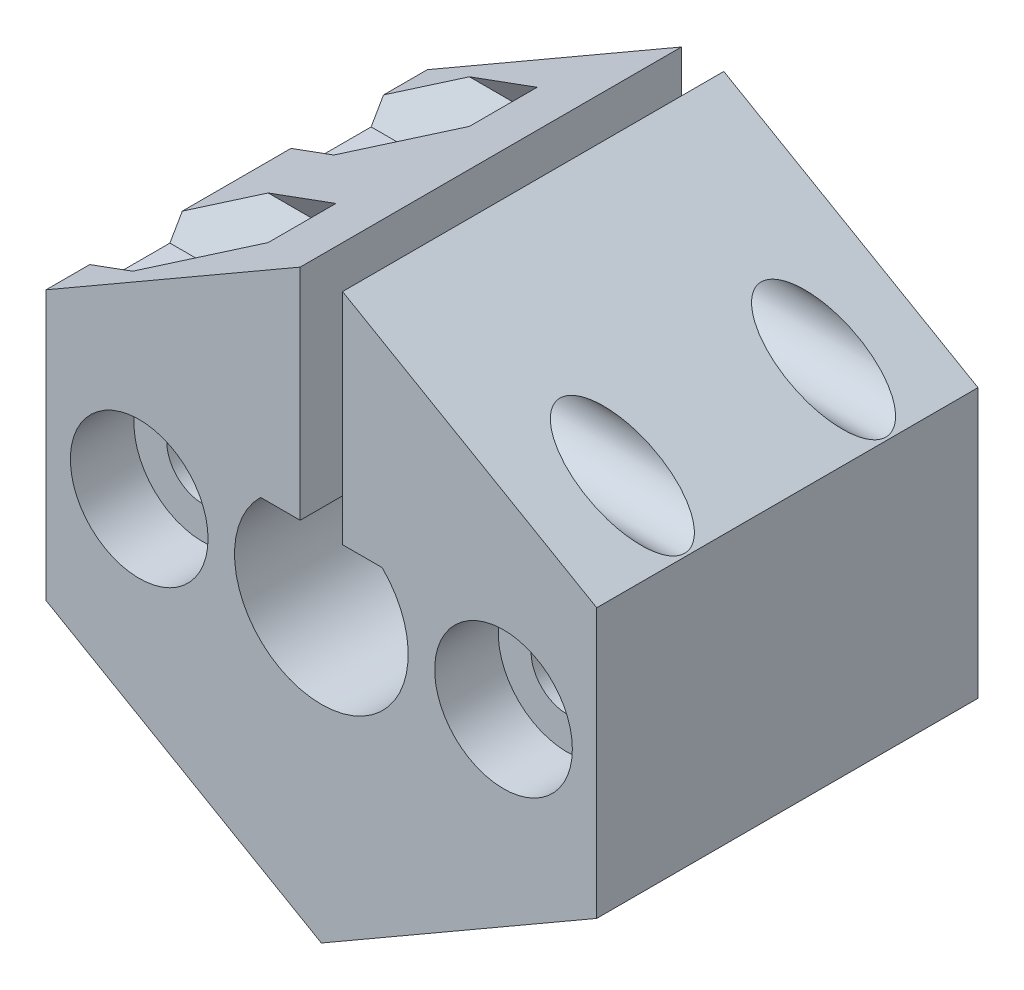
SolidWorks part; units mm, degrees
ref_plane "Front Plane" through (0, 0, 0) normal (1, 0, 0) x (0, 1, 0)
ref_plane "Top Plane" through (0, 0, 0) normal (0, 0, 1) x (0, 1, 0)
ref_plane "Right Plane" through (0, 0, 0) normal (0, 1, 0) x (-1, 0, 0)
sketch "Sketch1" plane through (0, 0, 0) normal (0, 0, 1) x (0, 1, 0)
  line L0 (11.7143, 0) -> (-11.7143, 0) construction
  line L1 (0, 4.1) -> (0, 0) construction
  line L7 (2.9286, 2.8694) -> (2.9286, 1)
  line L9 (2.9286, -1) -> (2.9286, -2.8694)
  line L10 (6.3509, -13) -> (-6.3509, -13)
  line L11 (-13.8564, 0) -> (-6.3509, -13)
  line L12 (-6.9282, -12) -> (6.9282, -12) construction
  line L13 (6.3509, -13) -> (13.2791, -1)
  line L14 (13.2791, 1) -> (6.3509, 13)
  line L15 (6.9282, 12) -> (-6.9282, 12) construction
  line L16 (-6.3509, 13) -> (-13.8564, 0)
  line L17 (13.2791, 1) -> (2.9286, 1)
  line L18 (13.2791, -1) -> (2.9286, -1)
  line L20 (6.3509, 13) -> (-6.3509, 13)
  arc A1 (2.9286, 2.8694) -> (-4.1, 0) centre (0, 0) ccw
  arc A2 (-4.1, 0) -> (2.9286, -2.8694) centre (0, 0) ccw
  circle A3 centre (0, 0) radius 12 construction
  point P6 (0, 0)
  point P9 (0, 0)
  point P12 (0, 4.1)
  point P13 (0, 4.1)
  point P21 (2.9286, 0)
  point P26 (8.2516, 0)
  point P29 (8.2516, 1)
  point P32 (8.2516, -1)
  point P34 (0, 13)
  dimension "D1" = 4.1
extrude "Boss-Extrude1" add sketch "Sketch1" along normal blind 18 contours A2 A1 L7 L9 region at (-4.1438, -1.6917, 0)
ref_plane "Plane1" through (-12, 0, 0) normal (1, 0, 0) x (0, 1, 0)
sketch "Sketch41" plane through (0, 0, 0) normal (0, 0, 1) x (0, 1, 0)
  line L0 (0, 11) -> (0, 4.1) construction
  line L1 (0, -4.1) -> (0, -11) construction
  circle A0 centre (0, 0) radius 11.7143 construction
  arc A1 (2.9286, 2.8694) -> (2.9286, -2.8694) centre (0, 0) ccw construction
  arc A2 (2.9286, 2.8694) -> (2.9286, -2.8694) centre (0, 0) ccw construction
  circle A3 centre (0, 0) radius 11.7143 construction
  circle A4 centre (0, 8.6) radius 1.7
  circle A5 centre (0, -8.6) radius 1.7
extrude "Cut-Extrude7" cut sketch "Sketch41" along normal blind 18
ref_plane "nut vertical" through (0, 7.77, 0) normal (0, 1, 0) x (-1, 0, 0)
ref_plane "Plane21" through (0, 0, 9) normal (0, 0, 1) x (0, 1, 0)
hole_wizard "CBORE for M3 SHCS1" positions "3DSketch1" profile "Sketch47" counterbore size "M3" standard "ANSI Metric" end condition through all
sketch3d "3DSketch1"
  line L0 (-8.6, 0, 18) -> (-8.6, 0, 0) construction
  point P0 (-8.6, 0, 18)
sketch "Sketch47" plane through (-8.6, 0, 18) normal (1, 0, 0) x (0, -1, 0)
  line L0 (0, 0) -> (0, 18)
  line L1 (0, 18) -> (1.7, 18)
  line L3 (1.7, 18) -> (1.7, 3)
  line L4 (1.7, 3) -> (3.25, 3)
  line L5 (3.25, 3) -> (3.25, 0)
  line L7 (3.25, 0) -> (0, 0)
  line L11 (0, -6.35) -> (0, 107.95) construction
  dimension "Thru Hole Dia." = 3.4
  dimension "Thru Hole Depth" = 18
  dimension "C'Bore Dia." = 6.5
  dimension "C'Bore Depth" = 3
hole_wizard "CBORE for M3 SHCS2" positions "3DSketch3" profile "Sketch49" counterbore size "M3" standard "ANSI Metric" end condition through all
sketch3d "3DSketch3"
  line L0 (8.6, 0, 18) -> (8.6, 0, 0) construction
  point P0 (8.6, 0, 18)
sketch "Sketch49" plane through (8.6, 0, 18) normal (1, 0, 0) x (0, -1, 0)
  line L0 (0, 0) -> (0, 18)
  line L1 (0, 18) -> (1.7, 18)
  line L3 (1.7, 18) -> (1.7, 3)
  line L4 (1.7, 3) -> (3.25, 3)
  line L5 (3.25, 3) -> (3.25, 0)
  line L7 (3.25, 0) -> (0, 0)
  line L11 (0, -6.35) -> (0, 107.95) construction
  dimension "Thru Hole Dia." = 3.4
  dimension "Thru Hole Depth" = 18
  dimension "C'Bore Dia." = 6.5
  dimension "C'Bore Depth" = 3
ref_plane "Plane22" through (-1, 0, 0) normal (1, 0, 0) x (0, 1, 0)
ref_plane "Plane23" through (-8, 0, 0) normal (1, 0, 0) x (0, 1, 0)
sketch "Sketch50" plane through (-8, 0, 0) normal (1, 0, 0) x (0, 1, 0)
  line L0 (0, 0) -> (0, 18) construction
  line L19 (0, 9) -> (-13.8564, 9) construction
  line L20 (-13.8564, 18) -> (-13.8564, 0) construction
  line L40 (-1, 0) -> (-1, 18) construction
  line L42 (8.1064, 0) -> (8.1064, 4.25) construction
  line L43 (8.1064, 18) -> (8.1064, 13.75) construction
  line L44 (8.1064, 0) -> (8.1064, 18) construction
  line L45 (5.3364, 5.8493) -> (5.3364, 2.6507)
  line L46 (5.3364, 2.6507) -> (8.1064, 1.0515)
  line L47 (8.1064, 1.0515) -> (10.8764, 2.6507)
  line L48 (10.8764, 2.6507) -> (10.8764, 5.8493)
  line L49 (10.8764, 5.8493) -> (8.1064, 7.4485)
  line L50 (5.3364, 15.3493) -> (8.1064, 16.9485)
  line L51 (5.3364, 12.1507) -> (5.3364, 15.3493)
  line L52 (8.1064, 10.5515) -> (5.3364, 12.1507)
  line L53 (10.8764, 12.1507) -> (8.1064, 10.5515)
  line L54 (10.8764, 15.3493) -> (10.8764, 12.1507)
  line L55 (8.1064, 16.9485) -> (10.8764, 15.3493)
  line L56 (8.1064, 7.4485) -> (5.3364, 5.8493)
  circle A2 centre (8.1064, 4.25) radius 2.85 construction
  circle A3 centre (8.1064, 13.75) radius 2.85 construction
  point P33 (-1, 9)
extrude "Cut-Extrude9" cut sketch "Sketch50" against normal blind 5 and the other way blind 4
sketch "Sketch51" plane through (-8, 0, 0) normal (1, 0, 0) x (0, 1, 0)
  circle A0 centre (8.1064, 13.75) radius 1.7
  circle A1 centre (8.1064, 4.25) radius 1.7
  dimension "D1" = 3.4
  dimension "D2" = 3.4
extrude "Cut-Extrude10" cut sketch "Sketch51" along normal blind 24 and the other way blind 6
